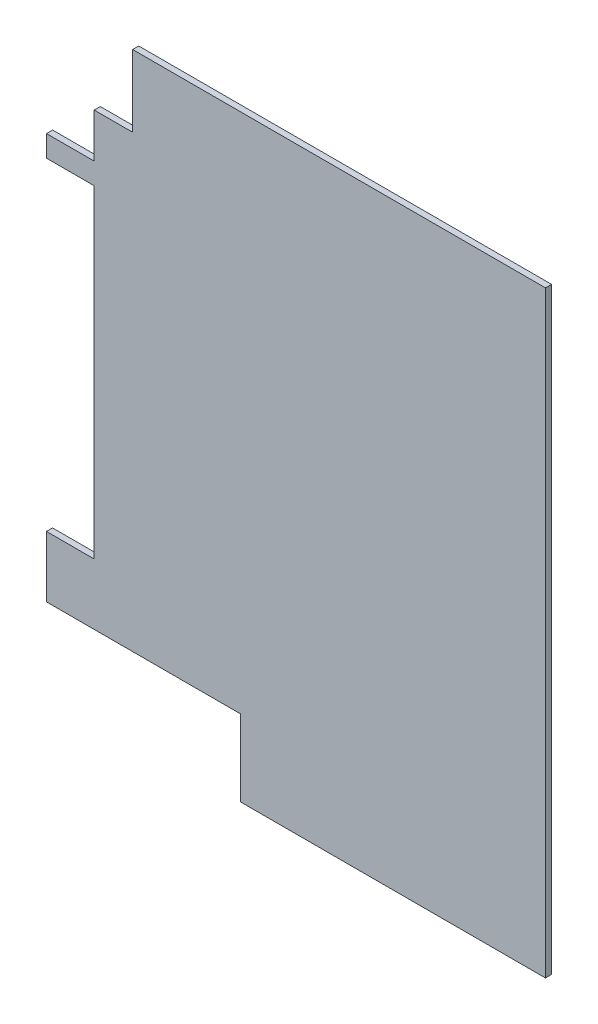
SolidWorks part; units mm, degrees
material "Balsa"
ref_plane "Front Plane" through (0, 0, 0) normal (0, 0, 1) x (1, 0, 0)
ref_plane "Top Plane" through (0, 0, 0) normal (0, 1, 0) x (1, 0, 0)
ref_plane "Right Plane" through (0, 0, 0) normal (1, 0, 0) x (0, 0, -1)
sketch "Sketch1" plane through (0, 0, 0) normal (0, 0, 1) x (1, 0, 0)
  line L0 (-5.7823, -13) -> (25.5, -13)
  line L2 (-5.7823, 1) -> (-5.7823, -13)
  line L5 (24.5, -14) -> (-24.5, -14) construction
  line L6 (321.5, -265) -> (321.5, 30)
  line L7 (-5.8246, -265) -> (65.6329, -265)
  line L8 (-5.8246, -265) -> (-5.8246, -225)
  line L11 (-5.8246, -265) -> (65.6329, -225) construction
  line L12 (-5.8246, -225) -> (65.6329, -265) construction
  line L15 (321.5, -265) -> (25.5, -265)
  line L16 (25.5, 1) -> (25.5, -265)
  line L17 (-5.8246, -225) -> (25.5, -225)
  line L18 (-24.5, -224) -> (24.5, -224) construction
  line L19 (-5.7823, 1) -> (25.5, 1)
  line L20 (24.5, -224) -> (24.5, -14) construction
  line L21 (-85.1981, 31) -> (50.7481, 31) construction
  line L23 (25.5, 1) -> (25.5, 30)
  line L24 (25.5, 30) -> (321.5, 30)
  line L27 (277.3251, 57) -> (277.3251, -295) construction
  line L28 (26.2777, -266) -> (-26.2882, -266) construction
  line L30 (-63.4467, 81) -> (255.5737, 81) construction
  line L31 (50.7481, 30) -> (321.5, 30)
  line L32 (50.7481, 30) -> (50.7481, 77)
  line L33 (50.7481, 77) -> (321.5, 77)
  line L34 (321.5, 30) -> (321.5, 77)
  line L35 (50.7481, 30) -> (321.5, 77) construction
  line L36 (50.7481, 77) -> (321.5, 30) construction
  line L37 (255.5737, -319) -> (-63.4467, -319) construction
  line L38 (321.5, -265) -> (121.5, -265)
  line L39 (321.5, -265) -> (321.5, -315)
  line L40 (321.5, -315) -> (121.5, -315)
  line L41 (121.5, -265) -> (121.5, -315)
  line L42 (321.5, -265) -> (121.5, -315) construction
  line L43 (321.5, -315) -> (121.5, -265) construction
  line L44 (50.7481, 31) -> (50.7481, -269) construction
  point P4 (32.4695, -6)
  point P10 (29.9042, -245)
  point P15 (48.1318, -132)
  point P24 (48.1318, 15.5)
  point P36 (186.1241, 53.5)
  point P42 (221.5, -290)
  dimension "D1" = 1
  dimension "D2" = 1
  dimension "D3" = 1
  dimension "D4" = 1
  dimension "D5" = 1
  dimension "D6" = 31.3246
  dimension "D7" = 296
  dimension "D8" = 4
  dimension "D9" = 200
  dimension "D10" = 4
extrude "Boss-Extrude1" add sketch "Sketch1" along normal blind 4 contours L24 L23 L16 L7 L15 L6 | L19 L2 L0 L16 | L17 L8 L7 L16 | L24 L34 L33 L32 | L15 L41 L40 L39 region at (9.8589, -6, 0) region at (173.5, -117.5, 0) region at (9.8377, -245, 0) region at (186.1241, 53.5, 0) region at (221.5, -290, 0)
